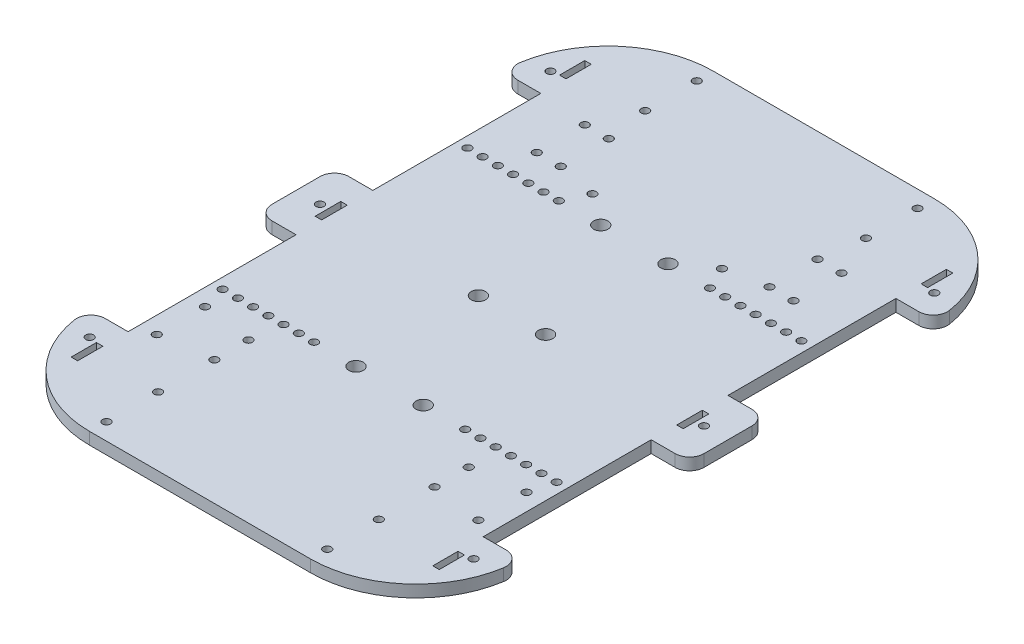
SolidWorks part; units mm, degrees
ref_plane "Ön Düzlem" through (0, 0, 0) normal (0, 0, 1) x (1, 0, 0)
ref_plane "Üst Düzlem" through (0, 0, 0) normal (0, 1, 0) x (1, 0, 0)
ref_plane "Sağ Düzlem" through (0, 0, 0) normal (1, 0, 0) x (0, 0, -1)
sketch "Sketch2" plane through (0, 0, 0) normal (0, 1, 0) x (1, 0, 0)
  line L0 (-74, -86) -> (-74, -51) construction
  line L1 (46, -130) -> (-46, -130)
  line L2 (90, -10) -> (90, 10)
  line L3 (46, 130) -> (-46, 130)
  line L4 (-90, -10) -> (-90, 10)
  line L5 (90, -130) -> (-90, 130) construction
  line L6 (90, 130) -> (-90, -130) construction
  line L7 (-83.5233, 86) -> (-74, 86)
  line L9 (-84, 16) -> (-74, 16)
  line L10 (-74, 86) -> (-74, 16)
  line L11 (-83.5233, -86) -> (-74, -86)
  line L13 (-84, -16) -> (-74, -16)
  line L14 (-74, -86) -> (-74, -16)
  line L15 (83.5233, 86) -> (74, 86)
  line L17 (84, 16) -> (74, 16)
  line L18 (74, 86) -> (74, 16)
  line L19 (83.5233, -86) -> (74, -86)
  line L21 (84, -16) -> (74, -16)
  line L22 (74, -86) -> (74, -16)
  line L23 (-74, 51) -> (74, 51) construction
  line L24 (-74, -51) -> (74, -51) construction
  line L26 (-74, 96.51) -> (-76.7, 96.51)
  line L27 (-76.7, 96.51) -> (-76.7, 107.02)
  line L28 (-74, 107.02) -> (-76.7, 107.02)
  line L29 (-74, 96.51) -> (-74, 107.02)
  line L30 (74, 96.51) -> (74, 107.02)
  line L31 (74, 107.02) -> (76.7, 107.02)
  line L32 (76.7, 96.51) -> (76.7, 107.02)
  line L33 (74, 96.51) -> (76.7, 96.51)
  line L34 (74, -107.02) -> (76.7, -107.02)
  line L35 (76.7, -96.51) -> (76.7, -107.02)
  line L36 (74, -96.51) -> (74, -107.02)
  line L37 (74, -96.51) -> (76.7, -96.51)
  line L38 (-74, -96.51) -> (-74, -107.02)
  line L39 (-74, -107.02) -> (-76.7, -107.02)
  line L40 (-76.7, -96.51) -> (-76.7, -107.02)
  line L41 (-74, -96.51) -> (-76.7, -96.51)
  line L42 (-74, 5.3333) -> (-74, -5.3333)
  line L43 (74, 5.3333) -> (74, -5.3333)
  line L44 (-74, 5.3333) -> (-76.7, 5.3333)
  line L45 (-76.7, 5.3333) -> (-76.7, -5.3333)
  line L46 (-76.7, -5.3333) -> (-74, -5.3333)
  line L47 (74, 5.3333) -> (76.7, 5.3333)
  line L48 (76.7, 5.3333) -> (76.7, -5.3333)
  line L49 (76.7, -5.3333) -> (74, -5.3333)
  arc A2 (-46, -130) -> (-89.4481, -92.9474) centre (-46, -86) cw
  arc A3 (-89.4481, 92.9474) -> (-46, 130) centre (-46, 86) cw
  arc A4 (89.4481, 92.9474) -> (46, 130) centre (46, 86) ccw
  arc A5 (89.4481, -92.9474) -> (46, -130) centre (46, -86) cw
  arc A6 (-84, 16) -> (-90, 10) centre (-84, 10) ccw
  arc A7 (-84, -16) -> (-90, -10) centre (-84, -10) cw
  arc A8 (90, 10) -> (84, 16) centre (84, 10) ccw
  arc A9 (90, -10) -> (84, -16) centre (84, -10) cw
  arc A10 (-89.4481, -92.9474) -> (-83.5233, -86) centre (-83.5233, -92) cw
  arc A11 (83.5233, -86) -> (89.4481, -92.9474) centre (83.5233, -92) cw
  arc A12 (-89.4481, 92.9474) -> (-83.5233, 86) centre (-83.5233, 92) ccw
  arc A13 (89.4481, 92.9474) -> (83.5233, 86) centre (83.5233, 92) cw
  point P0 (0, 0)
  point P34 (-90, -16)
  point P39 (90, -16)
  point P46 (-90, 86)
  point P49 (90, 86)
  dimension "D3" = 44
  dimension "D4" = 44
  dimension "D5" = 44
  dimension "D6" = 44
  dimension "D15" = 6
  dimension "D16" = 6
  dimension "D17" = 6
  dimension "D18" = 6
  dimension "D19" = 6
  dimension "D20" = 6
  dimension "D21" = 6
  dimension "D22" = 6
  dimension "D1" = 260
  dimension "D2" = 180
  dimension "D7" = 16
  dimension "D8" = 70
  dimension "D9" = 16
  dimension "D10" = 70
  dimension "D11" = 70
  dimension "D12" = 16
  dimension "D13" = 16
  dimension "D14" = 70
extrude "Boss-Extrude4" add sketch "Sketch2" along normal blind 5
sketch "Sketch5" plane through (0, 5, 0) normal (0, 1, 0) x (1, 0, 0)
  line L0 (-53.5, 63.83) -> (-43.5, 63.83) construction
  line L1 (-43.5, 63.83) -> (-43.5, 83.83) construction
  line L2 (-43.5, 83.83) -> (-43.5808, 83.8151) construction
  line L3 (-43.5808, 83.8151) -> (-53.5, 83.83) construction
  line L4 (-74, 86) -> (-74, 16) construction
  line L5 (53.5, 83.83) -> (43.5, 83.83) construction
  line L6 (43.5, 83.83) -> (43.5, 63.83) construction
  line L7 (43.5, 63.83) -> (53.5, 63.83) construction
  line L8 (74, 16) -> (74, 86) construction
  line L9 (46, 130) -> (-46, 130) construction
  circle A0 centre (-69.6, -51) radius 1.65
  circle A1 centre (-63.25, -51) radius 1.65
  circle A2 centre (-56.9, -51) radius 1.65
  circle A3 centre (-50.55, -51) radius 1.65
  circle A4 centre (-44.2, -51) radius 1.65
  circle A5 centre (-37.85, -51) radius 1.65
  circle A6 centre (-31.5, -51) radius 1.65
  circle A7 centre (31.5, -51) radius 1.65
  circle A8 centre (37.85, -51) radius 1.65
  circle A9 centre (44.2, -51) radius 1.65
  circle A10 centre (50.55, -51) radius 1.65
  circle A11 centre (56.9, -51) radius 1.65
  circle A12 centre (63.25, -51) radius 1.65
  circle A13 centre (69.6, -51) radius 1.65
  circle A14 centre (69.6, 51) radius 1.65
  circle A15 centre (63.25, 51) radius 1.65
  circle A16 centre (56.9, 51) radius 1.65
  circle A17 centre (50.55, 51) radius 1.65
  circle A18 centre (44.2, 51) radius 1.65
  circle A19 centre (37.85, 51) radius 1.65
  circle A20 centre (31.5, 51) radius 1.65
  circle A21 centre (-31.5, 51) radius 1.65
  circle A22 centre (-37.85, 51) radius 1.65
  circle A23 centre (-44.2, 51) radius 1.65
  circle A24 centre (-50.55, 51) radius 1.65
  circle A25 centre (-56.9, 51) radius 1.65
  circle A26 centre (-63.25, 51) radius 1.65
  circle A27 centre (-69.6, 51) radius 1.65
  circle A29 centre (-14, -51) radius 3
  circle A30 centre (14, -51) radius 3
  circle A31 centre (14, 51) radius 3
  circle A32 centre (-14, 51) radius 3
  circle A33 centre (-14, 0) radius 3
  circle A34 centre (14, 0) radius 3
  circle A35 centre (-80, 96) radius 1.65
  circle A36 centre (-80, 0) radius 1.65
  circle A37 centre (80, 0) radius 1.65
  circle A38 centre (-80, -96) radius 1.65
  circle A39 centre (80, -96) radius 1.65
  circle A40 centre (80, 96) radius 1.65
  circle A45 centre (-53.5, 83.83) radius 1.65
  circle A46 centre (-53.5, 63.83) radius 1.65
  circle A47 centre (-43.5, 63.83) radius 1.65
  circle A48 centre (-43.5, 83.83) radius 1.65
  circle A49 centre (43.5, 63.83) radius 1.65
  circle A50 centre (53.5, 63.83) radius 1.65
  circle A51 centre (43.5, 83.83) radius 1.65
  circle A52 centre (53.5, 83.83) radius 1.65
  circle A53 centre (-46, 123) radius 1.65
  circle A54 centre (-46, 101.5) radius 1.65
  circle A55 centre (46, 101.5) radius 1.65
  circle A56 centre (46, 123) radius 1.65
  circle A61 centre (-67, -60.96) radius 1.65
  circle A62 centre (-45.8971, -63.9231) radius 1.65
  circle A63 centre (-67, -81.04) radius 1.65
  circle A64 centre (-45.8971, -78.1568) radius 1.65
  circle A65 centre (45.8971, -63.9231) radius 1.65
  circle A66 centre (45.8971, -78.1568) radius 1.65
  circle A67 centre (67, -81.04) radius 1.65
  circle A68 centre (67, -60.96) radius 1.65
  circle A69 centre (46, -123) radius 1.65
  circle A70 centre (46, -101.5) radius 1.65
  circle A71 centre (-46, -101.5) radius 1.65
  circle A72 centre (-46, -123) radius 1.65
  circle A73 centre (-27, 60.5) radius 1.65
  circle A74 centre (27, 60.5) radius 1.65
  dimension "D1" = 20.5
  dimension "D2" = 20.5
  dimension "D3" = 46.17
  dimension "D4" = 66.17
  dimension "D5" = 66.17
extrude "Cut-Extrude1" cut sketch "Sketch5" against normal through all
